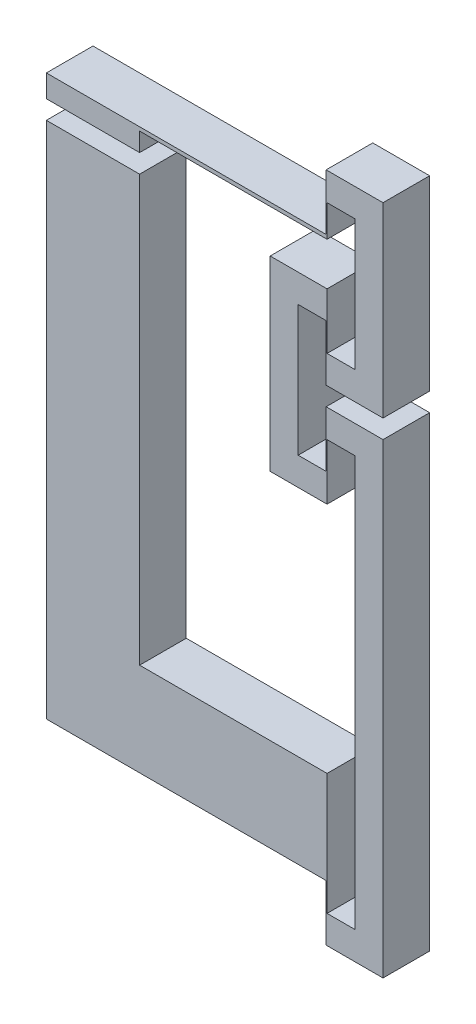
SolidWorks part; units mm, degrees
ref_plane "Front Plane" through (0, 0, 0) normal (0, 0, 1) x (1, 0, 0)
ref_plane "Top Plane" through (0, 0, 0) normal (0, 1, 0) x (1, 0, 0)
ref_plane "Right Plane" through (0, 0, 0) normal (1, 0, 0) x (0, 0, -1)
sketch "Sketch1" plane through (0, 0, 0) normal (0, 0, 1) x (1, 0, 0)
  line L0 (0, 0) -> (0, 55.6)
  line L4 (10, 10) -> (10, 55.6)
  line L5 (10, 55.6) -> (0, 55.6)
  line L6 (0, 57.6) -> (0, 60)
  line L7 (0, 60) -> (30, 60)
  line L8 (30.1, 60) -> (30.1, 59.6)
  line L9 (30.1, 59.6) -> (10, 59.6)
  line L10 (10, 59.6) -> (10, 57.6)
  line L11 (10, 57.6) -> (0, 57.6)
  line L12 (10, 10) -> (30.1, 10)
  line L20 (33.1, -3) -> (33.1, 41)
  line L24 (36.1, 44) -> (36.1, -6)
  line L32 (24, 35) -> (24, 55)
  line L33 (24, 55) -> (30.1, 55)
  line L36 (27, 52) -> (27, 38)
  line L41 (33.1, 63) -> (30.1, 63)
  line L44 (36.1, 66) -> (36.1, 46)
  line L47 (30.1, 60) -> (30.1, 63)
  line L48 (30, 60) -> (30, 66)
  line L49 (30, 66) -> (36.1, 66)
  line L55 (30.1, 55) -> (30.1, 52)
  line L78 (30.1, 49) -> (33.1, 49)
  line L82 (27, 52) -> (30, 52)
  line L83 (30.1, 52) -> (30.1, 49)
  line L84 (36.1, 46) -> (30, 46)
  line L85 (30, 46) -> (30, 52)
  line L86 (24, 35) -> (30.1, 35)
  line L87 (30.1, 35) -> (30.1, 36)
  line L88 (30, 38) -> (27, 38)
  line L89 (36.1, 44) -> (30, 44)
  line L91 (30.1, 41) -> (33.1, 41)
  line L92 (30.1, 36) -> (30.1, 41)
  line L97 (36.1, -6) -> (30, -6)
  line L98 (30, -6) -> (30, -3)
  line L100 (30, -3) -> (30, 0)
  line L101 (33.1, -3) -> (30.1, -3)
  line L105 (0, 0) -> (30, 0)
  line L108 (33.1, 63) -> (33.1, 49)
  line L109 (30, 44) -> (30, 38)
  line L110 (30.1, 10) -> (30.1, -3)
  point P4 (0, 0)
  point P17 (0, 0)
  dimension "D3" = 3
  dimension "D4" = 0.1
  dimension "D5" = 3
  dimension "D6" = 3
  dimension "D7" = 0.1
  dimension "D12" = 0.4
  dimension "D13" = 30
  dimension "D15" = 0.4
  dimension "D10" = 45.6
  dimension "D11" = 50
  dimension "D16" = 3
  dimension "D14" = 3
  dimension "D17" = 3
  dimension "D19" = 3
  dimension "D21" = 10
  dimension "D24" = 30
  dimension "D25" = 2.4
  dimension "D22" = 10
  dimension "D18" = 3
  dimension "D26" = 20
  dimension "D27" = 3
  dimension "D28" = 3
  dimension "D29" = 3
  dimension "D30" = 3
  dimension "D31" = 20
  dimension "D9" = 3
  dimension "D32" = 3
  dimension "D33" = 3
  dimension "D34" = 3
  dimension "D20" = 3
  dimension "D8" = 0.1
  dimension "D23" = 0.1
extrude "Boss-Extrude1" add sketch "Sketch1" along normal blind 5
equation "\"A.L\"= 0.05m"
equation "\"A.h\"= 0.003m"
equation "\"A.d\"= 0.003m"
equation "\"A.delta\"= 45.0001"
equation "\"A.w\"= 0.02m"
equation "\"A.v\"= 0.03m"
equation "\"B.L\"= 0.02m"
equation "\"B.h\"= 0.003m"
equation "\"C.h\"= 0.0004m"
equation "\"C.d\"= 0.003m"
equation "\"C.L\"= 0.02m"
equation "\"C.wmax\"= 0.002m"
equation "\"a_h\"= 0.0001m"
equation "\"a_d\"= 0.003m"
equation "\"a_L\"= 0.003m"
equation "\"b_h\"= 0.0001m"
equation "\"b_d\"= 0.003m"
equation "\"b_L\"= 0.003m"
equation "\"c_h\"= 0.0001m"
equation "\"c_d\"= 0.003m"
equation "\"c_L\"= 0.003m"
equation "\"S.h\"= 0.01m"
equation "\"S.L\"= 0.0478m"
equation "\"D4@Sketch1\"=\"c_h\""
equation "\"D5@Sketch1\"=\"c_L\""
equation "\"d_h\"= 0.0001m"
equation "\"d_L\"= 0.003m"
equation "\"d_d\"= 0.003m"
equation "\"D6@Sketch1\"=\"b_L\""
equation "\"D7@Sketch1\"=\"b_h\""
equation "\"D12@Sketch1\"=\"C.h\""
equation "\"D13@Sketch1\"=\"C.L\"+\"S.h\""
equation "\"D15@Sketch1\"=\"C.h\""
equation "\"A.t\"= 0.003m"
equation "\"A.s\"= 0.003m"
equation "\"D11@Sketch1\"=\"A.L\""
equation "\"D16@Sketch1\"=\"A.s\""
equation "\"D17@Sketch1\"=\"A.s\""
equation "\"D19@Sketch1\"=\"A.t\""
equation "\"D21@Sketch1\"=\"S.h\""
equation "\"D24@Sketch1\"=\"C.L\"+\"S.h\""
equation "\"D25@Sketch1\"=\"C.h\"+\"C.wmax\""
equation "\"D22@Sketch1\"=\"S.h\""
equation "\"D18@Sketch1\"=\"A.t\""
equation "\"B.t\"= 0.003m"
equation "\"B.s\"= 0.003m"
equation "\"D26@Sketch1\"=\"B.L\""
equation "\"D27@Sketch1\"=\"B.s\""
equation "\"D28@Sketch1\"=\"B.s\""
equation "\"D29@Sketch1\"=\"B.t\""
equation "\"D30@Sketch1\"=\"B.t\""
equation "\"D14@Sketch1\"=\"A.h\""
equation "\"D.L\"= 0.02m"
equation "\"D.h\"= 0.003m"
equation "\"D.s\"= 0.003m"
equation "\"D.t\"= 0.003m"
equation "\"D31@Sketch1\"=\"D.L\""
equation "\"D3@Sketch1\"=\"D.h\""
equation "\"D9@Sketch1\"=\"D.t\""
equation "\"D33@Sketch1\"=\"a_L\""
equation "\"D34@Sketch1\"=\"D.s\""
equation "\"D32@Sketch1\"=\"D.t\""
equation "\"D20@Sketch1\"=\"d_L\""
equation "\"D10@Sketch1\"=\"S.L\"-\"C.wmax\"-\"C.h\"/2"
equation "\"D8@Sketch1\"=\"d_h\""
equation "\"D23@Sketch1\"=\"d_h\""
